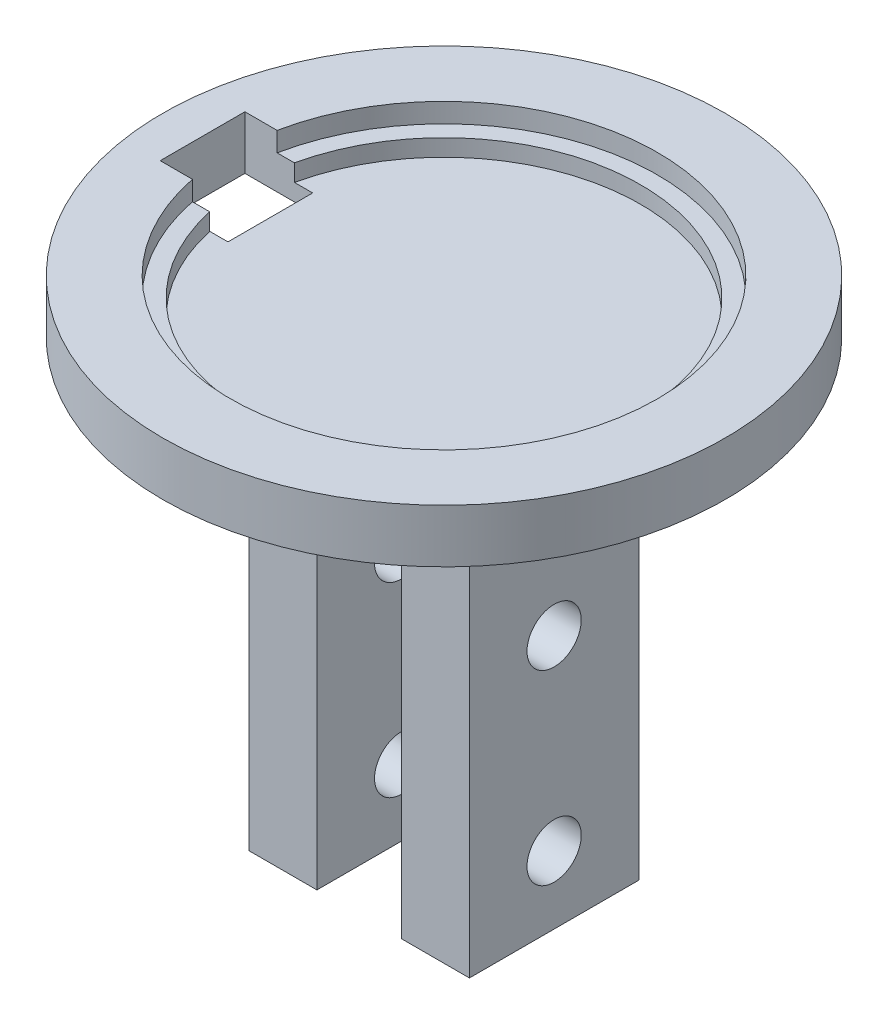
SolidWorks part; units mm, degrees
ref_plane "Front Plane" through (0, 0, 0) normal (0, 0, 1) x (1, 0, 0)
ref_plane "Top Plane" through (0, 0, 0) normal (0, 1, 0) x (1, 0, 0)
ref_plane "Right Plane" through (0, 0, 0) normal (1, 0, 0) x (0, 0, -1)
sketch "Sketch1" plane through (0, 0, 0) normal (0, 0, 1) x (1, 0, 0)
  line L0 (-14.45, -3.342) -> (-10.45, -3.342)
  line L1 (-10.45, -3.342) -> (-10.45, -4.492)
  line L2 (-10.45, -4.492) -> (-9.45, -4.492)
  line L3 (-9.45, -4.492) -> (-9.45, -5.492)
  line L4 (-9.45, -5.492) -> (2.15, -5.492)
  line L5 (-14.45, -3.342) -> (-14.45, -6.492)
  line L6 (-14.45, -6.492) -> (2.15, -6.492)
  line L7 (2.15, -6.492) -> (2.15, -5.492)
  dimension "D1" = 11.6
  dimension "D2" = 1
  dimension "D3" = 1
  dimension "D4" = 1
  dimension "D5" = 1.15
  dimension "D6" = 4
revolve "Revolve1" add sketch "Sketch1" angle 360 about L7
sketch "Sketch2" plane through (0, -6.492, 0) normal (0, -1, 0) x (1, 0, 0)
  line L0 (2.15, 16.6) -> (2.15, -16.6) construction
  line L1 (-14.45, 0) -> (18.75, 0) construction
  line L2 (8.65, -5) -> (4.65, -5)
  line L3 (-4.35, 5) -> (-0.35, 5)
  line L4 (-4.35, 5) -> (-4.35, -5)
  line L5 (-4.35, -5) -> (-0.35, -5)
  line L6 (-0.35, 5) -> (-0.35, -5)
  line L7 (-4.35, 5) -> (-0.35, -5) construction
  line L8 (-4.35, -5) -> (-0.35, 5) construction
  line L9 (4.65, 5) -> (4.65, -5)
  line L10 (8.65, 5) -> (4.65, 5)
  line L11 (8.65, 5) -> (8.65, -5)
  circle A0 centre (2.15, 0) radius 16.6 construction
  point P11 (-2.35, 0)
  dimension "D1" = 4
  dimension "D2" = 10
  dimension "D3" = 5
extrude "Boss-Extrude1" add sketch "Sketch2" along normal blind 27
sketch "Sketch3" plane through (-4.35, 0, 0) normal (-1, 0, 0) x (0, 0, 1)
  line L0 (0, -33.492) -> (0, -8.5072) construction
  line L1 (5, -33.492) -> (-5, -33.492) construction
  circle A0 centre (0, -29.492) radius 1.6
  circle A1 centre (0, -18.492) radius 1.6
  dimension "D1" = 3.2
  dimension "D2" = 3.2
  dimension "D3" = 4
  dimension "D4" = 11
extrude "Cut-Extrude1" cut sketch "Sketch3" against normal blind 22.3
fillet "Fillet1" radius 2.75 8 edges at (6.65, -6.492, -5) (-2.35, -6.492, -5) (6.65, -6.492, 5) (-2.35, -6.492, 5) (8.65, -6.492, 0) (4.65, -6.492, 0) (-0.35, -6.492, 0) (-4.35, -6.492, 0)
sketch "Sketch6" plane through (0, -6.492, 0) normal (0, -1, 0) x (1, 0, 0)
  line L0 (-7.1, 0) -> (-15.9092, 0) construction
  line L1 (-12.1, -2.5) -> (-8.1, -2.5)
  line L2 (-12.1, -2.5) -> (-12.1, 2.5)
  line L3 (-12.1, 2.5) -> (-8.1, 2.5)
  line L4 (-8.1, -2.5) -> (-8.1, 2.5)
  line L5 (-12.1, -2.5) -> (-8.1, 2.5) construction
  line L6 (-12.1, 2.5) -> (-8.1, -2.5) construction
  line L7 (-7.1, -7.75) -> (-7.1, 7.75) construction
  point P0 (-10.1, 0)
  dimension "D3" = 3
  dimension "D1" = 4
  dimension "D2" = 5
extrude "Cut-Extrude4" cut sketch "Sketch6" against normal blind 10
